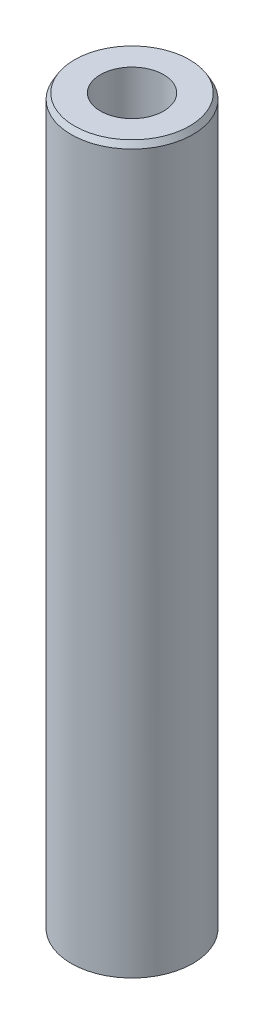
SolidWorks part; units mm, degrees
ref_plane "Front Plane" through (0, 0, 0) normal (0, 0, 1) x (1, 0, 0)
ref_plane "Top Plane" through (0, 0, 0) normal (0, 1, 0) x (1, 0, 0)
ref_plane "Right Plane" through (0, 0, 0) normal (1, 0, 0) x (0, 0, -1)
sketch "Sketch1" plane through (0, 0, 0) normal (0, 1, 0) x (1, 0, 0)
  circle A0 centre (0, 0) radius 35
  dimension "SHAFT_OD" = 70
extrude "Boss-Extrude1" add sketch "Sketch1" along normal blind 418.3773
sketch "Sketch2" plane through (0, 0, 0) normal (0, 1, 0) x (1, 0, 0)
  circle A0 centre (0, 0) radius 18.1895
  dimension "BORE_D" = 36.3789
extrude "Cut-Extrude1" cut sketch "Sketch2" along normal through all
chamfer "Chamfer1" distance 3.2959 angle 30 2 edges at (0, 418.3773, 35) (0, 0, 35) first distance on face at (0, 418.3773, 35) first distance on face at (0, 0, 18.1895)
